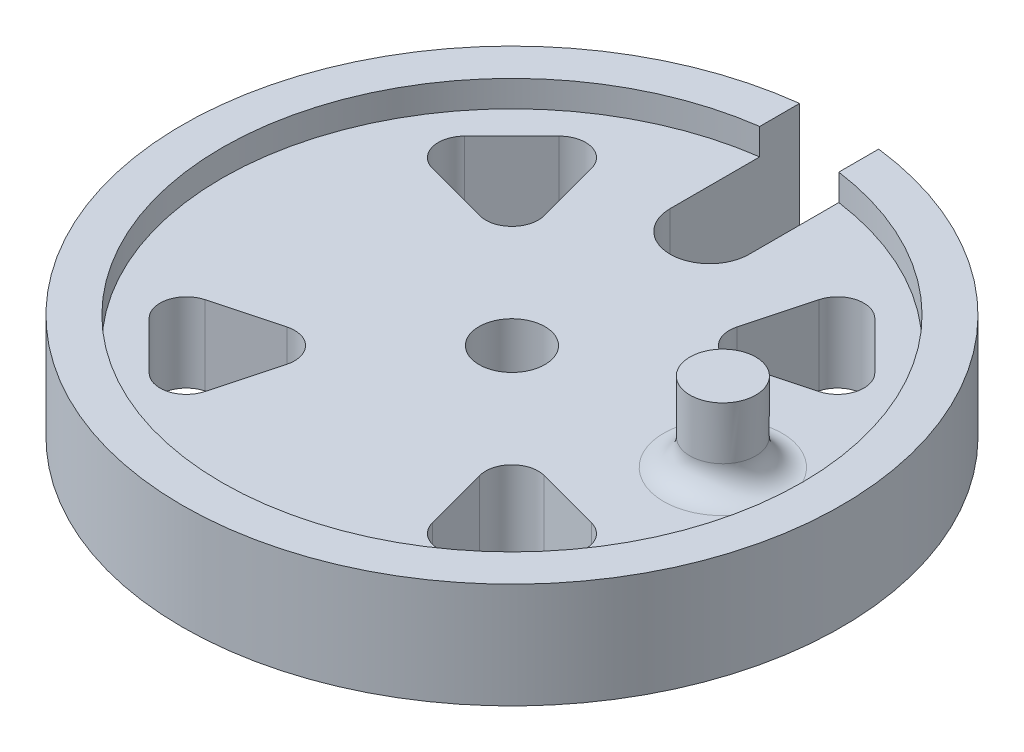
SolidWorks part; units mm, degrees
material "ABS"
ref_plane "Front Plane" through (0, 0, 0) normal (0, 0, 1) x (1, 0, 0)
ref_plane "Top Plane" through (0, 0, 0) normal (0, 1, 0) x (1, 0, 0)
ref_plane "Right Plane" through (0, 0, 0) normal (1, 0, 0) x (0, 0, -1)
sketch "Sketch1" plane through (0, 0, 0) normal (0, 1, 0) x (1, 0, 0)
  circle A0 centre (0, 0) radius 31.75
  dimension "D1" = 63.5
extrude "Boss-Extrude3" add sketch "Sketch1" along normal blind 10.16 contours A0
sketch "Sketch3" plane through (0, 10.16, 0) normal (0, 1, 0) x (1, 0, 0)
  circle A0 centre (0, 0) radius 27.94
  dimension "D1" = 55.88
extrude "Cut-Extrude1" cut sketch "Sketch3" against normal blind 2.54
sketch "Sketch4" plane through (0, 7.62, 0) normal (0, 1, 0) x (1, 0, 0)
  circle A0 centre (0, 0) radius 3.175
  dimension "D1" = 6.35
extrude "Cut-Extrude2" cut sketch "Sketch4" against normal through all
sketch "Sketch5" plane through (0, 7.62, 0) normal (0, 1, 0) x (1, 0, 0)
  line L0 (0, 0) -> (14.3684, 14.3684) construction
  line L1 (12.3962, 9.2854) -> (18.6179, 10.9525)
  line L2 (19.7566, 15.202) -> (15.202, 19.7566)
  line L3 (10.9525, 18.6179) -> (9.2854, 12.3962)
  line L4 (0, 0) -> (20.32, 0) construction
  line L5 (9.2854, -12.3962) -> (10.9525, -18.6179)
  line L6 (15.202, -19.7566) -> (19.7566, -15.202)
  line L7 (18.6179, -10.9525) -> (12.3962, -9.2854)
  line L8 (-12.3962, -9.2854) -> (-18.6179, -10.9525)
  line L9 (-19.7566, -15.202) -> (-15.202, -19.7566)
  line L10 (-10.9525, -18.6179) -> (-9.2854, -12.3962)
  line L11 (-9.2854, 12.3962) -> (-10.9525, 18.6179)
  line L12 (-15.202, 19.7566) -> (-19.7566, 15.202)
  line L13 (-18.6179, 10.9525) -> (-12.3962, 9.2854)
  line L14 (0, 0) -> (12.3962, 9.2854) construction
  line L15 (0, 0) -> (0, 8.6438) construction
  line L26 (-3.81, 19.05) -> (-3.81, 34.3743)
  line L27 (-3.81, 34.3743) -> (3.81, 34.3743)
  line L28 (3.81, 19.05) -> (3.81, 34.3743)
  line L29 (-3.81, 19.05) -> (3.81, 34.3743) construction
  line L30 (-3.81, 34.3743) -> (3.81, 19.05) construction
  circle A0 centre (14.3684, 14.3684) radius 4.3994 construction
  circle A1 centre (0, 0) radius 20.32 construction
  arc A2 (18.6179, 10.9525) -> (19.7566, 15.202) centre (17.9605, 13.4059) ccw
  arc A3 (9.2854, 12.3962) -> (12.3962, 9.2854) centre (11.7388, 11.7388) ccw
  arc A4 (15.202, 19.7566) -> (10.9525, 18.6179) centre (13.4059, 17.9605) ccw
  arc A5 (12.3962, -9.2854) -> (9.2854, -12.3962) centre (11.7388, -11.7388) ccw
  arc A6 (10.9525, -18.6179) -> (15.202, -19.7566) centre (13.4059, -17.9605) ccw
  arc A7 (19.7566, -15.202) -> (18.6179, -10.9525) centre (17.9605, -13.4059) ccw
  arc A8 (-9.2854, -12.3962) -> (-12.3962, -9.2854) centre (-11.7388, -11.7388) ccw
  arc A9 (-18.6179, -10.9525) -> (-19.7566, -15.202) centre (-17.9605, -13.4059) ccw
  arc A10 (-15.202, -19.7566) -> (-10.9525, -18.6179) centre (-13.4059, -17.9605) ccw
  arc A11 (-12.3962, 9.2854) -> (-9.2854, 12.3962) centre (-11.7388, 11.7388) ccw
  arc A12 (-10.9525, 18.6179) -> (-15.202, 19.7566) centre (-13.4059, 17.9605) ccw
  arc A13 (-19.7566, 15.202) -> (-18.6179, 10.9525) centre (-17.9605, 13.4059) ccw
  arc A14 (-3.81, 19.05) -> (3.81, 19.05) centre (0, 19.05) ccw
  point P6 (7.1842, 7.1842)
  point P12 (22.8674, 12.0911)
  point P17 (12.0911, 22.8674)
  point P18 (0, 26.7121)
  dimension "D2" = 40.64
  dimension "D3" = 2.54
  dimension "D1" = 15.24
  dimension "D4" = 45
  dimension "D6" = 15.4882
  dimension "D7" = 7.62
  dimension "D5" = 4
extrude "Cut-Extrude3" cut sketch "Sketch5" against normal through all
extrude "Cut-Extrude4" cut sketch "Sketch5<2>" along normal through all
sketch "Sketch5<2>" plane through (0, 7.62, 0) normal (0, 1, 0) x (1, 0, 0) same geometry as "Sketch5"
ref_plane "Plane1" through (0, 15.24, 0) normal (0, 1, 0) x (1, 0, 0)
sketch "Sketch6" plane through (0, 15.24, 0) normal (0, 1, 0) x (1, 0, 0)
  circle A0 centre (20.32, 0) radius 3.175
  circle A1 centre (0, 0) radius 20.32 construction
  point P5 (0, 0)
  dimension "D1" = 6.35
  dimension "D2" = 40.64
sketch "Sketch7" plane through (0, 7.62, 0) normal (0, 1, 0) x (1, 0, 0)
  circle A0 centre (20.32, 0) radius 3.175
  dimension "D1" = 6.35
loft "Loft4" add profiles "Sketch6", "Sketch7" connector at (21.645, 15.24, 2.8853) connector at (21.0922, 7.62, 3.0797)
fillet "Fillet1" radius 2.54 1 edges at (20.32, 7.62, 3.175)
